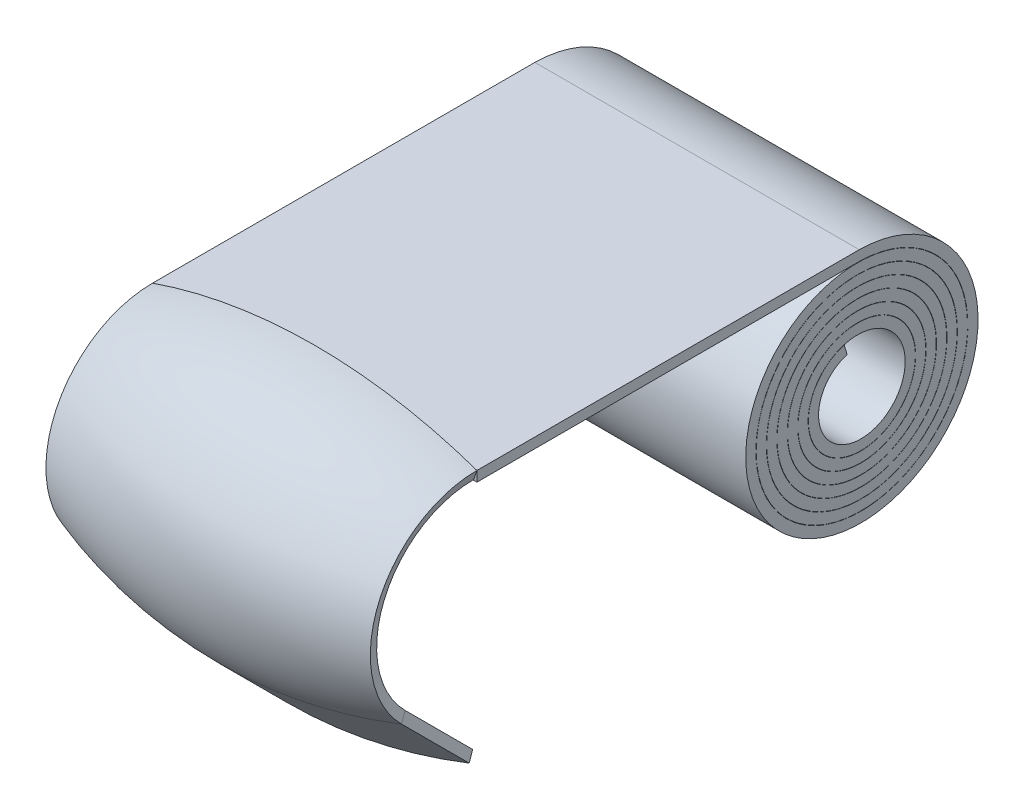
SolidWorks part; units mm, degrees
note: '?' marks a value the reader was unsure of.
ref_plane "Front Plane" through (0, 0, 0) normal (0, 0, 1) x (1, 0, 0)
ref_plane "Top Plane" through (0, 0, 0) normal (0, 1, 0) x (1, 0, 0)
ref_plane "Right Plane" through (0, 0, 0) normal (1, 0, 0) x (0, 0, -1)
ref_axis "Axis1" through (-9.9799, 0, 0) along (1, 0, 0)?
ref_plane "Plane1" through (0, 0, 0) normal (0, 0.7071, 0.7071) x (1, 0, 0)
sketch "Sketch1" plane through (0, 0, 0) normal (0, 0.7071, 0.7071) x (1, 0, 0)
  line L0 (0, 19.45) -> (-6.3639, 1.0706) construction
  line L1 (0, 19.45) -> (6.3639, 1.0706) construction
  line L2 (6.2331, 1.4486) -> (6.3639, 1.0706)
  line L3 (-6.2331, 1.4486) -> (-6.3639, 1.0706)
  arc A0 (-6.2331, 1.4486) -> (6.2331, 1.4486) centre (0, 19.45) ccw
  arc A1 (-6.3639, 1.0706) -> (6.3639, 1.0706) centre (0, 19.45) ccw
  arc A2 (-6.2985, 1.2596) -> (6.2985, 1.2596) centre (0, 19.45) ccw construction
  point P4 (0, 0.4)
  point P9 (-6.2985, 1.2596)
  point P10 (6.2985, 1.2596)
  point P11 (0, 0)
  dimension "D1" = 19.05
  dimension "D2" = 0.4
  dimension "D3" = 12.7
extrude "Boss-Extrude2" add sketch "Sketch1" along normal blind 3.75
sketch "Sketch4" plane through (0, 2.6517, 2.6517) normal (0, 0.7071, 0.7071) x (1, 0, 0)
  line L0 (-6.2331, 1.4486) -> (-6.3639, 1.0706)
  line L1 (6.2331, 1.4486) -> (6.3639, 1.0706)
  arc A0 (-6.2331, 1.4486) -> (6.2331, 1.4486) centre (0, 19.45) ccw
  arc A1 (-6.2331, 1.4486) -> (6.2331, 1.4486) centre (0, 19.45) ccw construction
  arc A2 (-6.3639, 1.0706) -> (6.3639, 1.0706) centre (0, 19.45) ccw
  arc A3 (-6.3639, 1.0706) -> (6.3639, 1.0706) centre (0, 19.45) ccw construction
sketch "Sketch3" plane through (0, 0, 0) normal (1, 0, 0) x (0, 0, -1)
  line L1 (-2.6517, 2.6517) -> (-2.1234, 2.1234) construction
  line L2 (-2.6517, 2.6517) -> (0, 0) construction
  line L3 (1.0632, 11.62) -> (-3.7164, 11.62) construction
  arc A0 (-2.6517, 2.6517) -> (1.0632, 11.62) centre (1.0632, 6.3665) cw
  point P7 (0.5858, 11.0922)
  point P8 (0.9936, 11.4521)
  point P10 (1.1161, 11.7479)
  point P13 (1.0632, 11.62)
  point P14 (-3.7905, 11.62)
  point P15 (0, 0)
  dimension "D2" = 11.62
  dimension "D1" = 12.3784
sweep "Sweep1" add profiles "Sketch4" path "Sketch3"
sketch "Sketch5" plane through (0, 0, -1.0632) normal (0, 0, -1) x (-1, 0, 0)
  line L1 (-6.3639, 10.5494) -> (6.3639, 10.5494)
  line L2 (-6.3639, 10.5494) -> (-6.3639, 10.1494)
  line L3 (-6.3639, 10.1494) -> (6.3639, 10.1494)
  line L4 (6.3639, 10.5494) -> (6.3639, 10.1494)
  point P5 (0, 0)
  point P6 (0, 0)
  point P7 (-4.8129, 9.5188)
  point P8 (-5.6449, 9.4663)
  point P9 (0, 0)
  point P10 (5.9287, 10.0285)
  point P12 (-5.01, 9.4663)
  dimension "D1" = 0.4
extrude "Boss-Extrude3" add sketch "Sketch5" along normal blind 15
sketch "Sketch7" plane through (0, 0, 0) normal (1, 0, 0) x (0, 0, -1)
  line L0 (14.8614, 10.5494) -> (17.2649, 10.5494) construction
  line L1 (16.0632, 10.5494) -> (1.0632, 10.5494) construction
  line L2 (16.0632, 5.7869) -> (16.0632, 15.3013) construction
  line L5 (16.0632, 10.5494) -> (16.0632, 10.1494) construction
  circle A0 centre (16.0632, 5.7869) radius 4.7625
  point P4 (16.0632, 10.5494)
  dimension "D1" = 9.525
curve "Helix/Spiral1"
sketch "Sketch9" plane through (0, 0, -16.0632) normal (0, 0, -1) x (-1, 0, 0)
  line L1 (-6.3639, 10.5494) -> (6.3639, 10.5494)
  line L2 (-6.3639, 10.5494) -> (-6.3639, 10.1494)
  line L3 (-6.3639, 10.1494) -> (6.3639, 10.1494)
  line L4 (6.3639, 10.5494) -> (6.3639, 10.1494)
sweep "Sweep2" add profiles "Sketch9" path "Helix/Spiral1"
equation "\"arcLength\" = 0.5in"
equation "\"tapeSpringThickness\"= 0.4mm"
equation "\"curvatureRadius\"= 0.75in"
equation "\"totalLength\"= 17.5cm"
equation "\"D2@Sketch1\"=\"tapeSpringThickness\""
equation "\"mountedLength\"= 3.75mm"
equation "\"transitionLength\" = 15mm"
equation "\"curvedLength\" = 12.4mm"
equation "\"D3@Sketch1\"=\"arcLength\""
equation "\"D1@Sketch1\"=\"curvatureRadius\""
equation "\"D1@Boss-Extrude2\"=\"mountedLength\""
equation "\"D1@Sketch5\"=\"tapeSpringThickness\""
equation "\"D1@Boss-Extrude3\"=\"transitionLength\""
equation "\"D1@Sketch7\"=\"arcLength\"*0.75"
equation "\"rolledLength\"= \"totalLength\" - \"mountedLength\" - \"transitionLength\" - \"curvedLength\""
equation "\"D1@Sketch3\"=\"curvedLength\""
